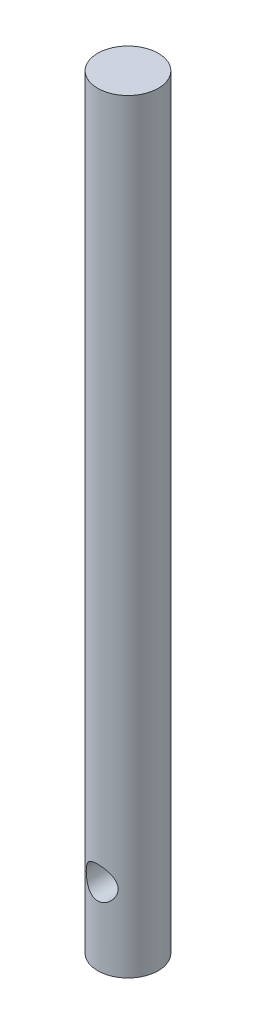
SolidWorks part; units mm, degrees
material "Plain Carbon Steel"
ref_plane "Front Plane" through (0, 0, 0) normal (0, 0, 1) x (1, 0, 0)
ref_plane "Top Plane" through (0, 0, 0) normal (0, 1, 0) x (1, 0, 0)
ref_plane "Right Plane" through (0, 0, 0) normal (1, 0, 0) x (0, 0, -1)
sketch "Sketch1" plane through (0, 0, 0) normal (0, 1, 0) x (1, 0, 0)
  circle A0 centre (0, 0) radius 4.7625
  dimension "D1" = 9.525
extrude "Boss-Extrude1" add sketch "Sketch1" along normal blind 120
sketch "Sketch2" plane through (0, 0, 0) normal (0, 0, 1) x (1, 0, 0)
  circle A0 centre (0, 12) radius 2.5
  dimension "D2" = 5
  dimension "D1" = 12
extrude "Cut-Extrude1" cut sketch "Sketch2" against normal mid plane 30
ref_axis "Axis1" through (0, 126, 0) along (0, -1, 0)
